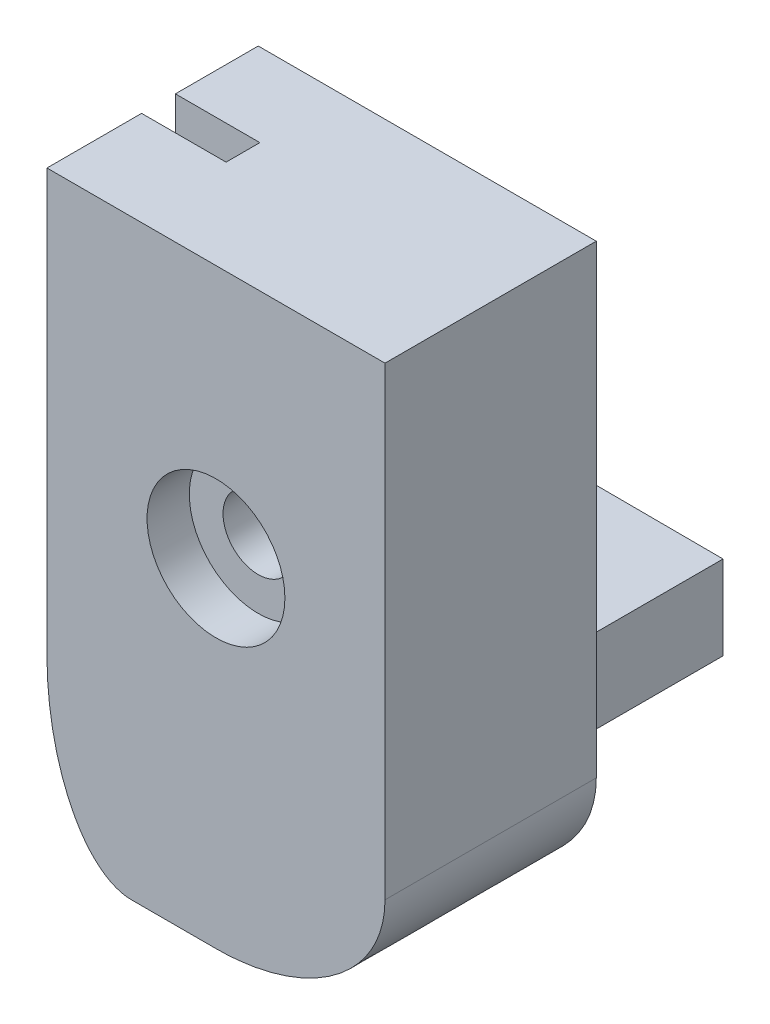
SolidWorks part; units mm, degrees
ref_plane "Ebene vorne" through (0, 0, 0) normal (0, 0, 1) x (1, 0, 0)
ref_plane "Ebene oben" through (0, 0, 0) normal (0, 1, 0) x (1, 0, 0)
ref_plane "Ebene rechts" through (0, 0, 0) normal (1, 0, 0) x (0, 0, -1)
sketch "Sketch1" plane through (0, 0, 0) normal (0, 0, 1) x (1, 0, 0)
  line L0 (-20, 0) -> (20, 0) construction
  line L1 (-20, 30) -> (20, 30)
  line L2 (-20, 30) -> (-20, -30)
  line L3 (-20, -30) -> (20, -30)
  line L4 (20, 30) -> (20, -30)
  line L5 (0, -30) -> (0, 30) construction
  point P9 (0, 0)
  dimension "D1" = 40
  dimension "D2" = 60
extrude "Boss-Extrude1" add sketch "Sketch1" along normal mid plane 25 contours L1 L4 L3 L2
sketch "Sketch3" plane through (0, 0, 0) normal (1, 0, 0) x (0, 0, -1)
  line L0 (-12.5, -8.1575) -> (-7.5, -8.1575)
  line L1 (-7.5, -8.1575) -> (-7.5, -4.1698)
  line L2 (-7.5, -4.1698) -> (7.5, -4.1698)
  line L3 (7.5, -4.1698) -> (7.5, -8.1575)
  line L4 (7.5, -8.1575) -> (12.5, -8.1575)
  line L5 (-12.5, 30) -> (-12.5, -30) construction
  line L6 (-19.1694, 0) -> (24.4545, 0) construction
  line L7 (-12.5, -8.1575) -> (-12.5, 0)
  line L8 (12.5, -8.1575) -> (12.5, 0)
  line L9 (-12.5, 0) -> (12.5, 0)
  dimension "D1" = 5
  dimension "D2" = 5
  dimension "D3" = 25
revolve "Cut-Revolve1" cut sketch "Sketch3" angle 360 about L6
sketch "Sketch4" plane through (-20, 0, 0) normal (-1, 0, 0) x (0, 0, 1)
  line L0 (12.5, 30) -> (-12.5, 30) construction
  line L1 (-2.6959, 30) -> (1.3041, 30)
  line L2 (-2.6959, 30) -> (-2.6959, -30)
  line L3 (-2.6959, -30) -> (1.3041, -30)
  line L4 (1.3041, 30) -> (1.3041, -30)
  line L5 (12.5, -30) -> (-12.5, -30) construction
  line L6 (-0.6959, 30) -> (-0.6959, -30) construction
  dimension "D1" = 4
extrude "Cut-Extrude1" cut sketch "Sketch4" against normal blind 10
sketch "Sketch5" plane through (0, 0, -12.5) normal (0, 0, 1) x (1, 0, 0)
  line L0 (0, -5.5) -> (-20, 1.7794)
  line L2 (-20, 30) -> (-20, -30) construction
  line L3 (0, -4.0953) -> (-20, 3.1841)
  line L5 (0, -5.5) -> (-20, -5.5) construction
  line L6 (0, -13.75) -> (0, 13.75) construction
  line L7 (-20, 3.1841) -> (-20, 1.7794)
  line L8 (0, -4.0953) -> (0, -5.5)
  circle A0 centre (0, 0) radius 5.5 construction
  point P12 (-10, -1.8603)
  dimension "D1" = 11
  dimension "D2" = 1.32
  dimension "D3" = 20
extrude "Cut-Extrude2" cut sketch "Sketch5" along normal blind 4
sketch "Sketch6" plane through (0, -30, 0) normal (0, 1, 0) x (1, 0, 0)
  line L1 (-20, 12.5) -> (20, 12.5)
  line L2 (-20, 12.5) -> (-20, -12.5)
  line L3 (-20, -12.5) -> (20, -12.5)
  line L4 (20, -12.5) -> (20, 12.5) construction
  line L5 (-20, 12.5) -> (20, 12.5) construction
  line L6 (-20, -12.5) -> (20, -12.5) construction
  line L7 (20, 12.5) -> (20, -12.5)
extrude "Boss-Extrude2" add sketch "Sketch6" against normal blind 10
fillet "Fillet1" radius 10 1 edges at (-20, -40, 0) second distance 20 first distance on face at (0, -40, 0)
sketch "Sketch7" plane through (0, 0, -12.5) normal (0, 0, -1) x (-1, 0, 0)
  line L0 (0, -30.0686) -> (18.6611, -30.0002)
  line L1 (0, 13.75) -> (0, -13.75) construction
  line L2 (0, -40) -> (10, -40)
  line L5 (0, -40) -> (0, -30.0686)
  line L6 (0, -30.0686) -> (0.4135, -29.7387)
  spline S0 degree 2 poles (-276.5679, 1938.4946) (-56.601, -81.0762) (12.889, -39.1472) (14.0837, -38.4263) (15.1542, -37.1387) (16.8677, -35.0778) (18.0536, -31.8557) (19.039, -29.1784) (19.5385, -26.0059) (48.5547, 158.3027) (-1746.6648, 906.47) knots -6.020804 -6.020804 -6.020804 0.125 0.125 0.25 0.25 0.5 0.5 0.75 0.75 16.46737 16.46737 16.46737 only from (10, -40) to (20, -20) construction
  spline S1 degree 2 poles (10, -40) (11.4756, -40) (12.889, -39.1472) (14.0837, -38.4263) (15.1542, -37.1387) (16.8677, -35.0778) (18.0536, -31.8557) (18.3848, -30.9559) (18.6611, -30.0002) knots 0 0 0 0.125 0.125 0.25 0.25 0.5 0.5 0.584019 0.584019 0.584019
extrude "Extrude-Thin1" [suppressed] add sketch "Sketch7" along normal blind 20 thin contours L5 thin type one direction wall 10
extrude "Boss-Extrude3" add sketch "Sketch7<5>" along normal blind 35 contours L0 S1 L2 L5
sketch "Sketch7<5>" plane through (0, 0, -12.5) normal (0, 0, -1) x (-1, 0, 0) same geometry as "Sketch7"
fillet "Fillet2" radius 20 1 edges at (20, -40, 0) second distance 15 first distance on face at (1.4286, -40, -16.0714)
fillet "Fillet3" radius 6 1 edges
